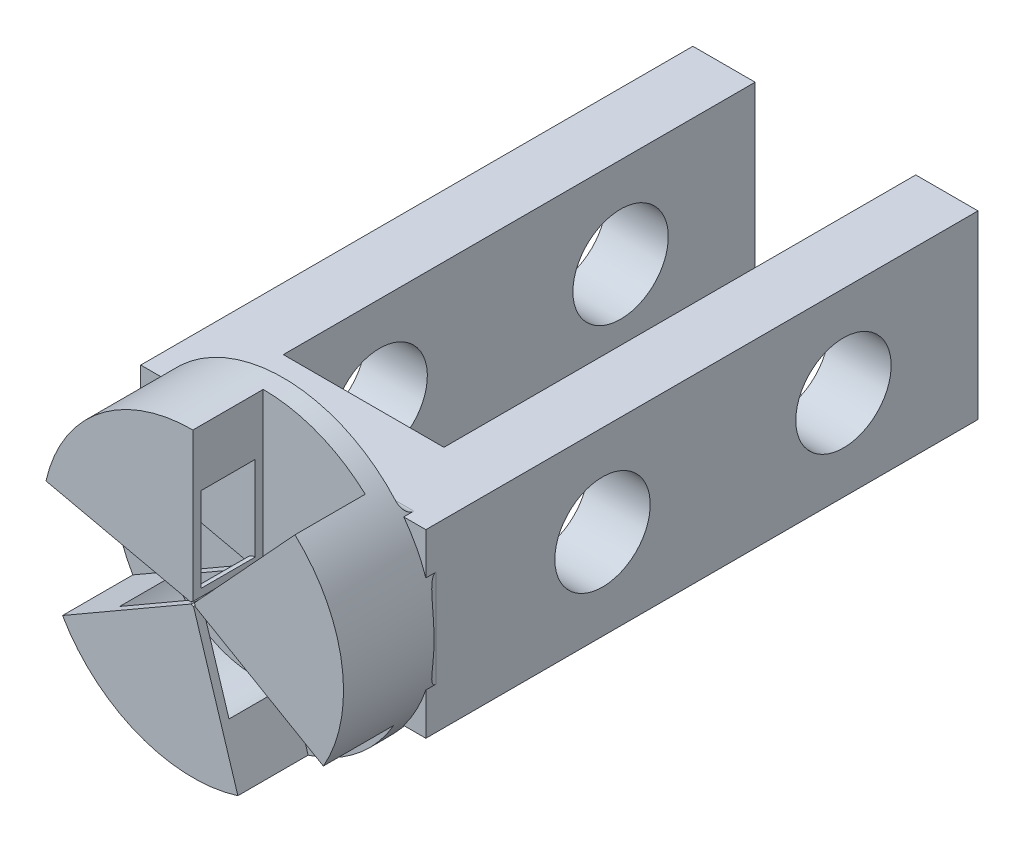
SolidWorks part; units mm, degrees
ref_plane "Plan de face" through (0, 0, 0) normal (0, 0, 1) x (1, 0, 0)
ref_plane "Plan de dessus" through (0, 0, 0) normal (0, 1, 0) x (1, 0, 0)
ref_plane "Plan de droite" through (0, 0, 0) normal (1, 0, 0) x (0, 0, -1)
sketch "Esquisse1" plane through (0, 0, 0) normal (0, 0, 1) x (1, 0, 0)
  line L1 (-7.1, 4.5) -> (7.1, 4.5)
  line L2 (-7.1, 4.5) -> (-7.1, -4.5)
  line L3 (-7.1, -4.5) -> (7.1, -4.5)
  line L4 (7.1, 4.5) -> (7.1, -4.5)
  line L5 (-7.1, 4.5) -> (7.1, -4.5) construction
  line L6 (-7.1, -4.5) -> (7.1, 4.5) construction
  point P0 (0, 0)
  dimension "D1" = 9
  dimension "D2" = 14.2
extrude "Boss.-Extru.3" add sketch "Esquisse1" along normal blind 4 contours L3 L4 L1 L2
sketch "Esquisse4" plane through (0, 0, 0) normal (0, 0, -1) x (-1, 0, 0)
  line L0 (7.1, -4.5) -> (-7.1, -4.5) construction
  line L1 (7.1, 4.5) -> (4, 4.5)
  line L2 (7.1, 4.5) -> (7.1, -4.5)
  line L3 (7.1, -4.5) -> (4, -4.5)
  line L4 (4, 4.5) -> (4, -4.5)
  line L5 (0, -4.5) -> (0, 4.5) construction
  line L6 (7.1, 4.5) -> (-7.1, 4.5) construction
  line L7 (-7.1, -4.5) -> (-4, -4.5)
  line L8 (-7.1, 4.5) -> (-7.1, -4.5)
  line L9 (-7.1, 4.5) -> (-4, 4.5)
  line L10 (-4, 4.5) -> (-4, -4.5)
  line L12 (7.1, 4.5) -> (7.1, -4.5) construction
  dimension "D1" = 3.1
extrude "Boss.-Extru.4" add sketch "Esquisse4" along normal blind 23.5
sketch "Esquisse5" plane through (-7.1, 0, 0) normal (-1, 0, 0) x (0, 0, 1)
  line L4 (0, -4.5) -> (0, 4.5)
  line L5 (0, 4.5) -> (-23.5, 4.5)
  line L6 (-23.5, 4.5) -> (-23.5, -4.5)
  line L7 (-23.5, -4.5) -> (0, -4.5)
  line L10 (-23.5, 4.5) -> (-23.5, -4.5) construction
  circle A0 centre (-16.8, 0) radius 2.375
  circle A2 centre (-4.8, 0) radius 2.375
  point P2 (-23.5, 0)
  dimension "D2" = 4.75
  dimension "D4" = 12
  dimension "D3" = 6.7
  dimension "D1" = 0
extrude "Enlèv. mat.-Extru.2" cut sketch "Esquisse5" against normal through all
sketch "Esquisse6" plane through (0, 0, 4) normal (0, 0, 1) x (1, 0, 0)
  circle A0 centre (0, 0) radius 7.5
  dimension "D1" = 15
extrude "Boss.-Extru.5" add sketch "Esquisse6" along normal blind 1 contours A0
fillet "Congé1" radius 0.5 4 edges at (7.1, 0, 4) (0, -4.5, 4) (-7.1, 0, 4) (0, 4.5, 4)
sketch "Esquisse8" plane through (0, 0, 5) normal (0, 0, 1) x (1, 0, 0)
  line L0 (0, 0) -> (0, 2) construction
  arc A0 (1.3547, 1.4714) -> (1.7321, -1) centre (0, 0) cw
  arc A1 (0.5969, -1.9089) -> (-1.7321, -1) centre (0, 0) cw
  circle A3 centre (0, 0) radius 2 construction
  arc A5 (-1.9516, 0.4375) -> (0, 2) centre (0, 0) cw
  point P12 (0, 0)
  dimension "D1" = 4
  dimension "D2" = 2.5
  dimension "D3" = 3
  dimension "D4" = 3
extrude "Extru.-Mince1" add sketch "Esquisse8" along normal blind 3.5 thin
sketch "Esquisse10" plane through (0, 0, 0) normal (0, 1, 0) x (1, 0, 0)
  line L0 (0, -2.6) -> (0, -7.6864) construction
  line L1 (0, -8.5) -> (0, -5) construction
  line L14 (-0.0976, -5) -> (-7.3184, -5)
  line L16 (-0.0976, -8.5) -> (-0.0976, -5)
  line L23 (-0.0976, -8.5) -> (-0.0976, -5) construction
  line L25 (-7.3184, -8.5) -> (-0.0976, -8.5)
  line L27 (-7.3184, -8.5) -> (-0.0976, -8.5)
  line L28 (-7.3184, -5) -> (-7.3184, -8.5)
  line L29 (4.68, -5.4) -> (0.4677, -5.4)
  line L30 (0.4677, -5.4) -> (0.4677, -8.1)
  line L31 (0.4677, -8.1) -> (4.68, -8.1)
  line L32 (4.68, -8.1) -> (4.68, -5.4)
  line L33 (4.68, -5.4) -> (0.4677, -5.4)
  line L34 (0.4677, -5.4) -> (0.4677, -8.1)
  line L35 (0.4677, -8.1) -> (4.68, -8.1)
  line L36 (4.68, -8.1) -> (4.68, -5.4)
  circle A0 centre (-4, -6.75) radius 0.5 construction
  point P12 (-4, -6.75)
  point P13 (-0.0976, -6.75)
  dimension "D1" = 1
  dimension "D3" = 4
  dimension "D2" = 0
  dimension "D4" = 0.4
revolve "Enlèvement de matière-Révolution1" cut sketch "Esquisse10" angle 360 about L0
